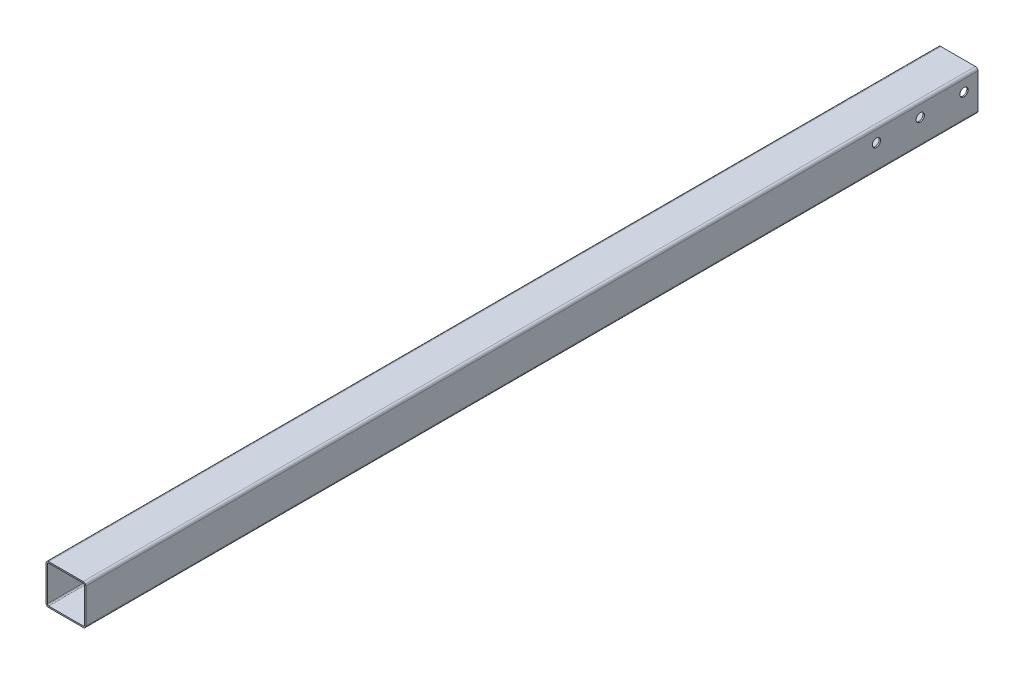
SolidWorks part; units mm, degrees
material "ASTM A500 Steel"
ref_plane "Front Plane" through (0, 0, 0) normal (0, 0, 1) x (1, 0, 0)
ref_plane "Top Plane" through (0, 0, 0) normal (0, 1, 0) x (1, 0, 0)
ref_plane "Right Plane" through (0, 0, 0) normal (1, 0, 0) x (0, 0, -1)
sketch "Sketch1" plane through (0, 0, 0) normal (0, 0, 1) x (1, 0, 0)
  line L1 (27.5336, 31.75) -> (-27.5336, 31.75)
  line L2 (31.75, 27.5336) -> (31.75, -27.5336)
  line L3 (27.5336, -31.75) -> (-27.5336, -31.75)
  line L4 (-31.75, 27.5336) -> (-31.75, -27.5336)
  line L5 (31.75, 31.75) -> (-31.75, -31.75) construction
  line L6 (31.75, -31.75) -> (-31.75, 31.75) construction
  line L7 (27.5336, 29.6418) -> (-27.5336, 29.6418)
  line L8 (29.6418, 27.5336) -> (29.6418, -27.5336)
  line L9 (27.5336, -29.6418) -> (-27.5336, -29.6418)
  line L10 (-29.6418, 27.5336) -> (-29.6418, -27.5336)
  line L11 (29.6418, 29.6418) -> (-29.6418, -29.6418) construction
  line L12 (29.6418, -29.6418) -> (-29.6418, 29.6418) construction
  arc A0 (-27.5336, -31.75) -> (-31.75, -27.5336) centre (-27.5336, -27.5336) cw
  arc A1 (31.75, -27.5336) -> (27.5336, -31.75) centre (27.5336, -27.5336) cw
  arc A2 (27.5336, 31.75) -> (31.75, 27.5336) centre (27.5336, 27.5336) cw
  arc A3 (-27.5336, 31.75) -> (-31.75, 27.5336) centre (-27.5336, 27.5336) ccw
  arc A4 (-27.5336, -29.6418) -> (-29.6418, -27.5336) centre (-27.5336, -27.5336) cw
  arc A5 (29.6418, -27.5336) -> (27.5336, -29.6418) centre (27.5336, -27.5336) cw
  arc A6 (27.5336, 29.6418) -> (29.6418, 27.5336) centre (27.5336, 27.5336) cw
  arc A7 (-27.5336, 29.6418) -> (-29.6418, 27.5336) centre (-27.5336, 27.5336) ccw
  point P0 (0, 0)
  point P6 (0, 0)
  dimension "D3" = 4.2164
  dimension "D4" = 2.1082
  dimension "D1" = 63.5
  dimension "D2" = 2.1082
extrude "Boss-Extrude1" add sketch "Sketch1" along normal blind 1422.4
hole_wizard "1/2 Clearance Hole1" positions "3DSketch1" profile "Sketch8" hole size "1/2" standard "ANSI Inch" end condition through all
sketch3d "3DSketch1"
  line L0 (31.75, 9.525, 22.225) -> (31.75, 9.525, 161.925) construction
  line L1 (31.75, 9.525, 22.225) -> (31.75, 9.525, 0) construction
  line L3 (31.75, -27.5336, 0) -> (31.75, 27.5336, 0) construction
  line L6 (0, 0, 0) -> (31.75, 0, 0) construction
  line L7 (31.75, 0, 0) -> (31.75, 9.525, 0) construction
  point P0 (31.75, 9.525, 22.225)
  point P2 (31.75, 9.525, 92.075)
  point P4 (31.75, 9.525, 161.925)
  dimension "D2" = 22.225
  dimension "D1" = 139.7
  dimension "D3" = 9.525
sketch "Sketch8" plane through (31.75, 9.525, 22.225) normal (0, 1, 0) x (0, 0, -1)
  line L0 (0, 0) -> (0, 63.5)
  line L1 (0, 63.5) -> (6.5481, 63.5)
  line L2 (6.5481, 63.5) -> (6.5481, 0)
  line L5 (6.5481, 0) -> (0, 0)
  line L11 (0, -6.35) -> (0, 107.95) construction
  dimension "Thru Hole Dia." = 13.0962
  dimension "Thru Hole Depth" = 63.5
sketch "Sketch9" plane through (0, -31.75, 0) normal (0, -1, 0) x (1, 0, 0)
  line L0 (-63.5473, 1041.4) -> (98.2559, 1041.4)
  line L1 (98.2559, 1016) -> (-68.4837, 1016)
  line L2 (-27.5336, 0) -> (27.5336, 0) construction
  dimension "D1" = 25.4
  dimension "D2" = 1016
split line "Split Line1" [suppressed]
sketch "Sketch10" [suppressed] plane through (-31.75, 0, 0) normal (-1, 0, 0) x (0, 0, 1)
  line L1 (-10.7461, 44.6478) -> (263.1986, 44.6478)
  line L2 (-10.7461, 44.6478) -> (-10.7461, -39.3699)
  line L3 (-10.7461, -39.3699) -> (263.1986, -39.3699)
  line L4 (263.1986, 44.6478) -> (263.1986, -39.3699)
  line L5 (126.2263, -39.3699) -> (126.2263, 44.6478) construction
  line L6 (-10.7461, 2.6389) -> (263.1986, 2.6389) construction
  point P904 (126.2263, 2.6389)
extrude "Cut-Extrude1" [suppressed] cut sketch "Sketch10" against normal through all flip side to cut
ref_axis "Axis1" [suppressed] through (29.6418, 9.525, 92.075) along (1, 0, 0)
sketch "Sketch11" [suppressed] plane through (0, 0, 0) normal (1, 0, 0) x (0, 0, -1)
  point P0 (-92.075, 9.525)
sketch "Sketch12" [suppressed] plane through (0, -31.75, 0) normal (0, -1, 0) x (1, 0, 0)
  line L1 (0, 0) -> (96.0595, 0)
  line L2 (0, 0) -> (0, 1451.2945)
  line L3 (0, 1451.2945) -> (96.0595, 1451.2945)
  line L4 (96.0595, 0) -> (96.0595, 1451.2945)
  line L5 (48.0297, 1451.2945) -> (48.0297, 0) construction
  line L6 (0, 725.6472) -> (96.0595, 725.6472) construction
  point P200 (48.0297, 725.6472)
extrude "Cut-Extrude2" [suppressed] cut sketch "Sketch12" against normal through all
equation "\"D3@Sketch1\"=0.083*2"
